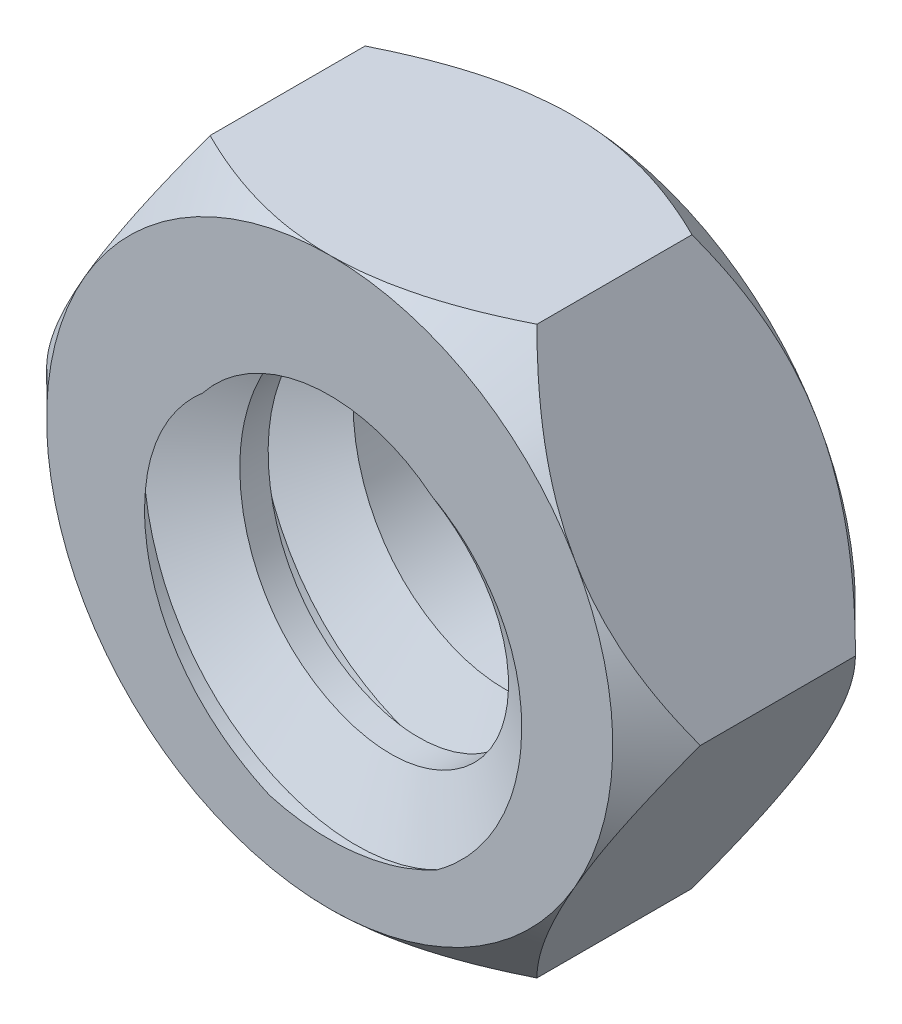
SolidWorks part; units mm, degrees
ref_plane "Front Plane" through (0, 0, 0) normal (0, 0, 1) x (1, 0, 0)
ref_plane "Top Plane" through (0, 0, 0) normal (0, 1, 0) x (1, 0, 0)
ref_plane "Right Plane" through (0, 0, 0) normal (1, 0, 0) x (0, 0, -1)
sketch "Sketch1" plane through (0, 0, 0) normal (0, 0, 1) x (1, 0, 0)
  line L0 (-2.0207, 0) -> (2.0207, 0) construction
  line L1 (2.0207, 0) -> (1.0104, 1.75)
  line L2 (1.0104, 1.75) -> (-1.0104, 1.75)
  line L3 (-1.0104, 1.75) -> (-2.0207, 0)
  line L4 (-2.0207, 0) -> (-1.0104, -1.75)
  line L5 (-1.0104, -1.75) -> (1.0104, -1.75)
  line L6 (1.0104, -1.75) -> (2.0207, 0)
  line L7 (0, -1.75) -> (0, 1.75) construction
  circle A0 centre (0, 0) radius 1.75
  circle A1 centre (0, 0) radius 1
  dimension "D1" = 3.5
  dimension "D2" = 2
extrude "Boss-Extrude1" add sketch "Sketch1" along normal blind 1.5 contours L3 L4 L5 L6 L1 L2
extrude "Cut-Extrude1" cut sketch "Sketch1<3>" along normal up to next contours A1
sketch "Sketch1<3>" plane through (0, 0, 0) normal (0, 0, 1) x (1, 0, 0) same geometry as "Sketch1"
extrude "Cut-Extrude2" cut sketch "Sketch1<4>" along normal blind 1 draft 45 flip side to cut contours A0
sketch "Sketch1<4>" plane through (0, 0, 0) normal (0, 0, 1) x (1, 0, 0) same geometry as "Sketch1"
ref_plane "Plane1" through (0, 0, 1.5) normal (0, 0, 1) x (1, 0, 0)
sketch "Sketch2" plane through (0, 0, 1.5) normal (0, 0, 1) x (1, 0, 0)
  circle A0 centre (0, 0) radius 1.75
  dimension "D1" = 3.5
extrude "Cut-Extrude3" cut sketch "Sketch2" against normal blind 1 draft 45 flip side to cut
thread "Thread1" pitch 0.7 method cut profile "Thread Profile1" start angle 0, offset 0, length 0, pitch 0.7, diameter 2
ref_plane "Plane2" through (1, 0, 0) normal (0, -1, 0) x (1, 0, 0)
sketch "Thread Profile1" plane through (1, 0, 0) normal (0, -1, 0) x (1, 0, 0)
  line L0 (0, 0) -> (0, 0.7) construction
  line L1 (0, 0) -> (0.3789, 0.2187)
  line L2 (0.3789, 0.2187) -> (0.3789, 0.3062)
  line L3 (0.3789, 0.3062) -> (0, 0.525)
  line L4 (0.3789, 0.2625) -> (0, 0.2625) construction
  line L11 (0, 0) -> (0, 0.525)
  point P2 (0, 0)
  dimension "Pitch" = 0.7
  dimension "Profile_Angle" = 60
  dimension "Profile_Land" = 0.0875
  dimension "Profile_Height" = 0.3789
